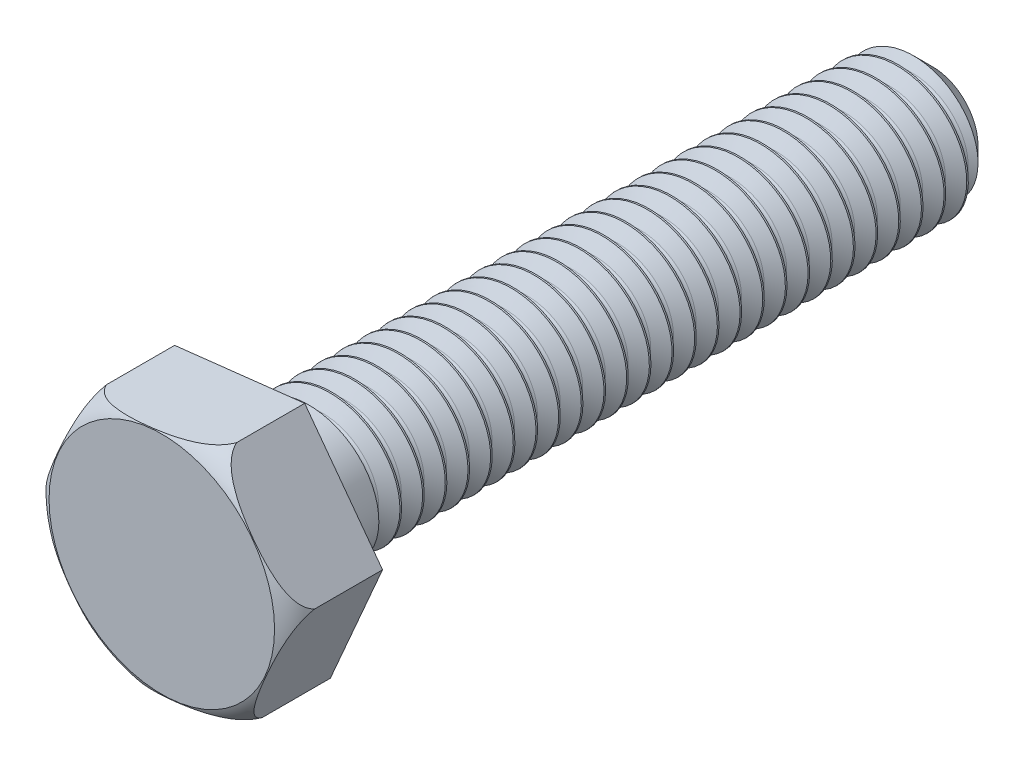
SolidWorks part; units mm, degrees
ref_plane "Ön Düzlem" through (0, 0, 0) normal (0, 0, 1) x (1, 0, 0)
ref_plane "Üst Düzlem" through (0, 0, 0) normal (0, 1, 0) x (1, 0, 0)
ref_plane "Sağ Düzlem" through (0, 0, 0) normal (1, 0, 0) x (0, 0, -1)
sketch "Sketch1" plane through (0, 0, 0) normal (0, 0, 1) x (1, 0, 0)
  circle A0 centre (0, 0) radius 3
extrude "Boss-Extrude1" add sketch "Sketch1" along normal blind 30
sketch "Sketch2" plane through (0, 0, 0) normal (0, 0, -1) x (-1, 0, 0)
  circle A0 centre (0, 0) radius 3
curve "Helix/Spiral1" pitch 1 height 27 turns 27
chamfer "Chamfer1" distance 1 angle 45 1 edges at (3, 0, 0)
sketch "Sketch3" plane through (0, 0, 0) normal (0, 1, 0) x (1, 0, 0)
  line L0 (0, 0) -> (-3, 0) construction
  line L1 (-3, 0) -> (-3, -0.93)
  line L4 (-3, 0) -> (-2.4046, -0.3438)
  line L5 (-3, -0.93) -> (-2.4046, -0.5862)
  arc A0 (-2.4046, -0.3438) -> (-2.4046, -0.5862) centre (-2.4746, -0.465) cw
  dimension "D1" = 0.14
sweep "Cut-Sweep1" cut profiles "Sketch3" path "Helix/Spiral1"
sketch "Sketch4" plane through (0, 0, 30) normal (0, 0, 1) x (1, 0, 0)
  line L1 (-5.7364, -0.6535) -> (-2.3023, -5.2946)
  line L2 (-2.3023, -5.2946) -> (3.4341, -4.6411)
  line L3 (3.4341, -4.6411) -> (5.7364, 0.6535)
  line L4 (5.7364, 0.6535) -> (2.3023, 5.2946)
  line L5 (2.3023, 5.2946) -> (-3.4341, 4.6411)
  line L6 (-3.4341, 4.6411) -> (-5.7364, -0.6535)
  circle A0 centre (0, 0) radius 5 construction
extrude "Boss-Extrude2" add sketch "Sketch4" along normal blind 4
sketch "Sketch5" plane through (0, 0, 34) normal (0, 0, 1) x (1, 0, 0)
  circle A0 centre (0, 0) radius 5
ref_plane "Plane1" through (0, 0, 0) normal (-0.1132, 0.9936, 0) x (0.9936, 0.1132, 0)
sketch "Sketch7" plane through (0, 0, 0) normal (-0.1132, 0.9936, 0) x (0.9936, 0.1132, 0)
  line L0 (-5.7735, -34) -> (-4.9735, -34)
  line L1 (-5.7735, -34) -> (-5.7735, -33)
  line L2 (-5.7735, -34) -> (-5.7735, -30) construction
  line L3 (0, -34) -> (0, -30.693) construction
  spline S0 degree 2 poles (-4.9735, -34) (-5.6163, -33.7026) (-5.7735, -33) knots 0 0 0 1 1 1
revolve "Cut-Revolve1" cut sketch "Sketch7" angle 360 about L3
